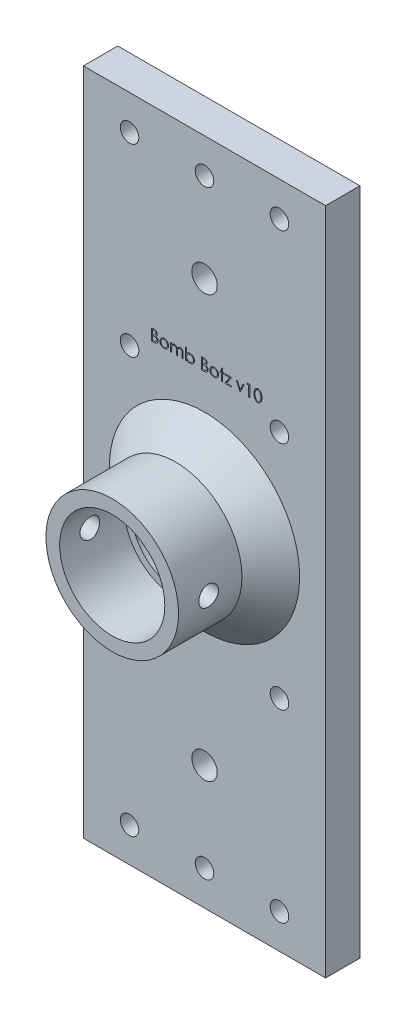
SolidWorks part; units mm, degrees
ref_plane "Front Plane" through (0, 0, 0) normal (0, 0, 1) x (1, 0, 0)
ref_plane "Top Plane" through (0, 0, 0) normal (0, 1, 0) x (1, 0, 0)
ref_plane "Right Plane" through (0, 0, 0) normal (1, 0, 0) x (0, 0, -1)
sketch "Sketch1" plane through (0, 0, 0) normal (0, 0, 1) x (1, 0, 0)
  line L5 (-33.3375, 92.075) -> (33.3375, 92.075)
  line L6 (-33.3375, 92.075) -> (-33.3375, -92.075)
  line L7 (-33.3375, -92.075) -> (33.3375, -92.075)
  line L8 (33.3375, 92.075) -> (33.3375, -92.075)
  line L9 (-33.3375, 92.075) -> (33.3375, -92.075) construction
  line L10 (-33.3375, -92.075) -> (33.3375, 92.075) construction
  point P5 (0, 0)
  dimension "D1" = 66.675
  dimension "D2" = 184.15
extrude "Boss-Extrude1" add sketch "Sketch1" along normal blind 4.7625 and the other way blind 4.699
sketch "Sketch3" plane through (0, 0, 4.7625) normal (0, 0, 1) x (1, 0, 0)
  circle A0 centre (0, 0) radius 6.35
  dimension "D1" = 12.7
extrude "Cut-Extrude1" cut sketch "Sketch3" against normal blind 0.508
sketch "Sketch4" plane through (0, 0, 4.7625) normal (0, 0, 1) x (1, 0, 0)
  circle A0 centre (0, 0) radius 18.2562
  dimension "D1" = 36.5125
extrude "Boss-Extrude2" add sketch "Sketch4" along normal blind 38.1 contours A0
sketch "Sketch5" plane through (0, 0, 42.8625) normal (0, 0, 1) x (1, 0, 0)
  circle A0 centre (0, 0) radius 12.4619
  dimension "D1" = 24.9237
extrude "Cut-Extrude2" cut sketch "Sketch5" against normal blind 38.1 contours A0
sketch "Sketch7" plane through (0, 0, 42.8625) normal (0, 0, 1) x (1, 0, 0)
  circle A0 centre (0, 0) radius 14.2875
  dimension "D1" = 28.575
extrude "Cut-Extrude3" cut sketch "Sketch7" against normal blind 30.48
hole_wizard "#10 Clearance Hole1" positions "Sketch8" profile "Sketch9" hole size "#10" standard "ANSI Inch" end condition up to next
sketch "Sketch8" plane through (0, 0, 4.7625) normal (0, 0, 1) x (1, 0, 0)
  line L0 (33.3375, 92.075) -> (-33.3375, 92.075) construction
  line L1 (33.3375, -92.075) -> (33.3375, 92.075) construction
  line L2 (-33.3375, 92.075) -> (-33.3375, -92.075) construction
  line L3 (-33.3375, -92.075) -> (33.3375, -92.075) construction
  point P0 (-20.6375, 82.55)
  point P2 (-20.6375, -82.55)
  point P4 (20.6375, -82.55)
  point P6 (20.6375, 82.55)
  point P23 (-20.6375, 31.75)
  point P26 (-20.6375, -31.75)
  point P28 (20.6375, -31.75)
  point P30 (20.6375, 31.75)
  point P31 (0, 82.55)
  point P33 (0, -82.55)
  dimension "D1" = 9.525
  dimension "D2" = 12.7
  dimension "D3" = 9.525
  dimension "D4" = 12.7
  dimension "D5" = 9.525
  dimension "D6" = 12.7
  dimension "D7" = 12.7
  dimension "D8" = 9.525
  dimension "D9" = 12.7
  dimension "D10" = 12.7
  dimension "D11" = 50.8
  dimension "D12" = 50.8
  dimension "D13" = 50.8
  dimension "D14" = 50.8
  dimension "D15" = 12.7
  dimension "D16" = 12.7
sketch "Sketch9" plane through (-20.6375, 82.55, 4.7625) normal (1, 0, 0) x (0, -1, 0)
  line L0 (0, 0) -> (0, 9.4615)
  line L1 (0, 9.4615) -> (2.5527, 9.4615)
  line L2 (2.5527, 9.4615) -> (2.5527, 0)
  line L5 (2.5527, 0) -> (0, 0)
  line L11 (0, -6.35) -> (0, 107.95) construction
  dimension "Thru Hole Dia." = 5.1054
  dimension "Thru Hole Depth" = 9.4615
sketch "Sketch10" plane through (0, 0, 4.7625) normal (0, 0, 1) x (1, 0, 0)
  line L0 (33.3375, 41.275) -> (-33.3375, 41.275)
  line L1 (33.3375, -92.075) -> (33.3375, 92.075) construction
  line L2 (-33.3375, 92.075) -> (-33.3375, -92.075) construction
  line L3 (33.3375, -41.275) -> (-33.3375, -41.275)
  point P8 (-33.3375, 0)
  dimension "D1" = 41.275
  dimension "D2" = 41.275
sketch "Sketch13" plane through (0, 0, 42.8625) normal (0, 0, 1) x (1, 0, 0)
  circle A0 centre (0, 0) radius 14.478
  dimension "D1" = 28.956
extrude "Cut-Extrude4" cut sketch "Sketch13" against normal up to surface (30.48 mm away) up to face at (14.2875, 0, 12.3825)
sketch "Sketch14" plane through (0, 0, 42.8625) normal (0, 0, 1) x (1, 0, 0)
  circle A0 centre (0, 0) radius 18.2562
extrude "Cut-Extrude5" cut sketch "Sketch14" against normal blind 12.7
sketch "Sketch15" plane through (0, -92.075, 0) normal (0, -1, 0) x (-1, 0, 0)
hole_wizard "#3 (0.213) Diameter Hole1" positions "3DSketch7" profile "Sketch22" hole size "#3" standard "ANSI Inch" end condition through all
sketch3d "3DSketch7"
  point P0 (18.2562, 0, 21.8735)
sketch "Sketch22" plane through (18.2562, 0, 21.8735) normal (0, 1, 0) x (0, 0, -1)
  line L0 (0, 0) -> (0, 51.5938)
  line L1 (0, 51.5938) -> (2.7051, 51.5938)
  line L2 (2.7051, 51.5938) -> (2.7051, 0)
  line L5 (2.7051, 0) -> (0, 0)
  line L11 (0, -6.35) -> (0, 107.95) construction
  dimension "Thru Hole Dia." = 5.4102
  dimension "Thru Hole Depth" = 51.5938
hole_wizard "CBORE for M6 Hex Head Bolt1" positions "Sketch25" profile "Sketch26" counterbore size "M6" standard "ANSI Metric" end condition through all
sketch "Sketch25" plane through (0, 0, -4.699) normal (0, 0, -1) x (-1, 0, 0)
  line L0 (-33.3375, 41.275) -> (33.3375, 41.275) construction
  line L1 (-33.3375, -41.275) -> (33.3375, -41.275) construction
  point P0 (0, -58.039)
  point P2 (0, 58.039)
  dimension "D1" = 16.764
  dimension "D2" = 16.764
sketch "Sketch26" plane through (0, -58.039, -4.699) normal (1, 0, 0) x (0, 1, 0)
  line L0 (0, 0) -> (0, 34.8615)
  line L1 (0, 34.8615) -> (3.5, 34.8615)
  line L3 (3.5, 34.8615) -> (3.5, 4.38)
  line L4 (3.5, 4.38) -> (7.275, 4.38)
  line L5 (7.275, 4.38) -> (7.275, 0)
  line L7 (7.275, 0) -> (0, 0)
  line L11 (0, -6.35) -> (0, 107.95) construction
  dimension "Thru Hole Dia." = 7
  dimension "Thru Hole Depth" = 34.8615
  dimension "C'Bore Dia." = 14.55
  dimension "C'Bore Depth" = 4.38
sketch "Sketch28" plane through (0, 0, 4.7625) normal (0, 0, 1) x (1, 0, 0)
  text T0 "Bomb Botz v10"
extrude "Boss-Extrude4" add sketch "Sketch28" against normal blind 1.27
chamfer "Chamfer1" distance 7.9375 distance2 7.9375 1 edges at (18.2562, 0, 4.7625)
sketch "Sketch29" plane through (0, 0, 4.7625) normal (0, 0, 1) x (1, 0, 0)
  text T0 "Bomb Botz v10"
extrude "Cut-Extrude6" cut sketch "Sketch29" against normal blind 1.27
